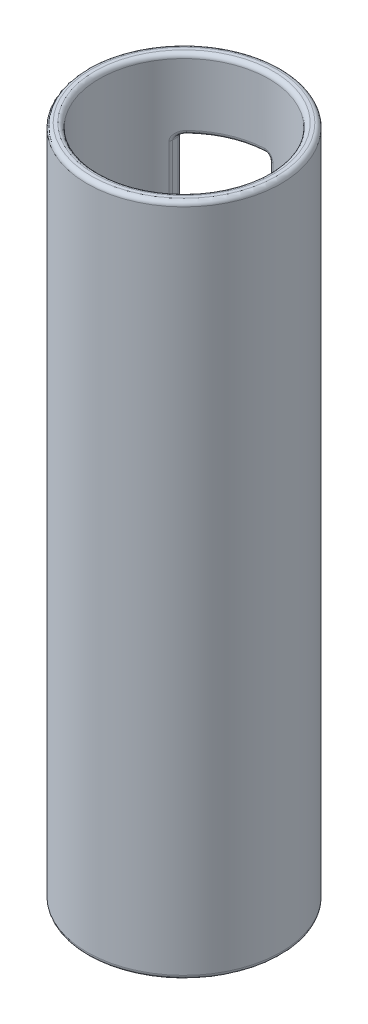
SolidWorks part; units mm, degrees
ref_plane "Front Plane" through (0, 0, 0) normal (0, 0, 1) x (1, 0, 0)
ref_plane "Top Plane" through (0, 0, 0) normal (0, 1, 0) x (1, 0, 0)
ref_plane "Right Plane" through (0, 0, 0) normal (1, 0, 0) x (0, 0, -1)
sketch "Sketch1" plane through (0, 0, 0) normal (0, 1, 0) x (1, 0, 0)
  circle A0 centre (0, 0) radius 22
  dimension "D1" = 44
extrude "Boss-Extrude1" add sketch "Sketch1" along normal blind 153
sketch "Sketch2" plane through (0, 153, 0) normal (0, 1, 0) x (1, 0, 0)
  circle A0 centre (0, 0) radius 19.25
  dimension "D1" = 38.5
extrude "Cut-Extrude1" cut sketch "Sketch2" against normal blind 150
sketch "Sketch3" plane through (0, 0, 0) normal (0, 0, 1) x (1, 0, 0)
  line L0 (0, 0) -> (0, 33.7672) construction
  line L2 (0, 16.8836) -> (-15, 16.8836)
  line L3 (0, 16.8836) -> (0, 136.8836)
  line L4 (0, 136.8836) -> (-15, 136.8836)
  line L5 (-15, 16.8836) -> (-15, 136.8836)
  dimension "D1" = 120
  dimension "D2" = 15
extrude "Cut-Extrude2" cut sketch "Sketch3" against normal blind 150
fillet "Fillet1" radius 1 15 edges at (0, 153, 22) (0, 153, 19.25) (0, 0, 22) (-8.0605, 136.8836, -20.4702) (-8.316, 136.8836, -17.3611) (-15, 76.8836, -16.0935) (-15, 76.8836, -12.0649) (-15, 136.8836, -14.0792) (-8.0605, 16.8836, -20.4702) (-8.316, 16.8836, -17.3611) (-15, 16.8836, -14.0792) (0, 76.8836, -22) (0, 136.8836, -20.625) (0, 76.8836, -19.25) (0, 16.8836, -20.625)
